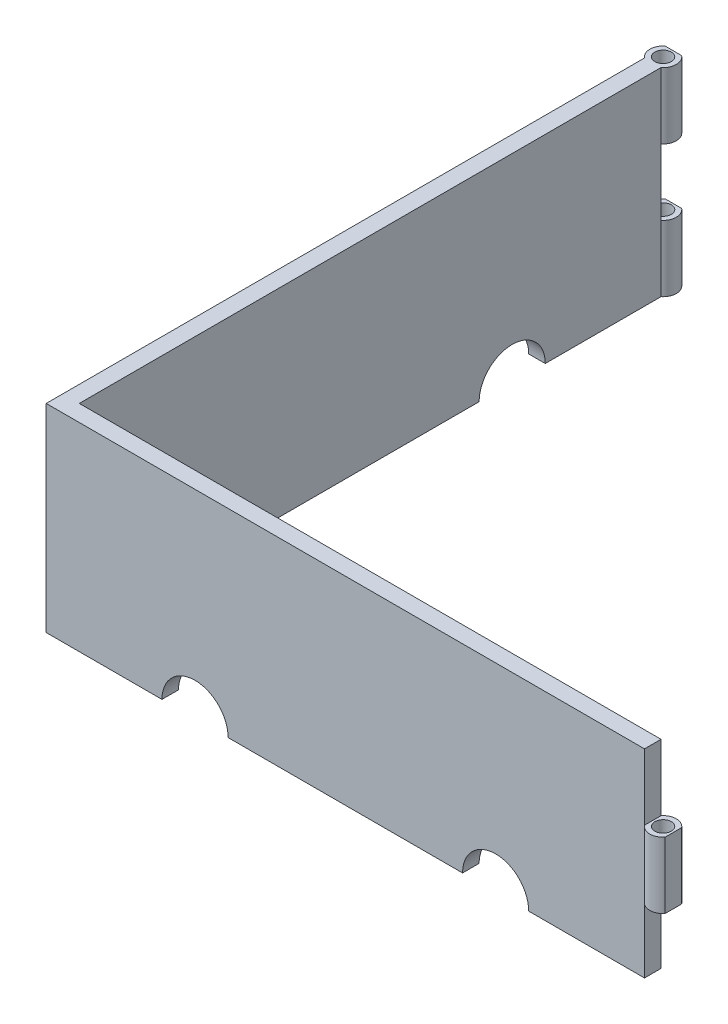
SolidWorks part; units mm, degrees
ref_plane "Front Plane" through (0, 0, 0) normal (0, 0, 1) x (1, 0, 0)
ref_plane "Top Plane" through (0, 0, 0) normal (0, 1, 0) x (1, 0, 0)
ref_plane "Right Plane" through (0, 0, 0) normal (1, 0, 0) x (0, 0, -1)
sketch "Sketch1" plane through (0, 0, 0) normal (0, 1, 0) x (1, 0, 0)
  line L0 (0, 0) -> (180, 0)
  line L1 (0, 0) -> (0, 180)
  line L3 (5, 180) -> (5, 5)
  line L4 (5, 5) -> (180, 5)
  line L6 (180, 5) -> (180.8775, 5)
  line L7 (180, 0) -> (180.8775, 0)
  line L8 (5, 180) -> (5, 180.8775)
  line L9 (0, 180) -> (0, 180.8775)
  arc A0 (180.8775, 0) -> (180.8775, 5) centre (184, 2.5) ccw
  arc A1 (5, 180.8775) -> (0, 180.8775) centre (2.5, 184) ccw
  dimension "D6" = 4
  dimension "D9" = 4
  dimension "D12" = 2.5
  dimension "D1" = 180
  dimension "D2" = 180
  dimension "D3" = 5
  dimension "D4" = 5
  dimension "D5" = 0.8775
  dimension "D7" = 0.8775
  dimension "D8" = 3.1225
  dimension "D10" = 0.8775
  dimension "D11" = 0.8775
extrude "Boss-Extrude1" add sketch "Sketch1" along normal blind 60
sketch "Sketch2" plane through (0, 60, 0) normal (0, 1, 0) x (1, 0, 0)
  circle A0 centre (184, 2.5) radius 2.5
  circle A1 centre (2.5, 184) radius 2.5
  dimension "D1" = 5
  dimension "D2" = 5
extrude "Cut-Extrude1" cut sketch "Sketch2" against normal blind 50
sketch "Sketch4" plane through (0, 0, 0) normal (0, 0, 1) x (1, 0, 0)
  line L0 (180.8775, 0) -> (188, 0)
  line L1 (188, 0) -> (188, 20)
  line L2 (188, 0) -> (188, 60) construction
  line L3 (188, 20) -> (180.8775, 20)
  line L4 (180.8775, 60) -> (180.8775, 0) construction
  line L5 (180.8775, 20) -> (180.8775, 0)
  line L6 (180.8775, 60) -> (188, 60)
  line L7 (188, 60) -> (188, 40)
  line L8 (188, 40) -> (180.8775, 40)
  line L9 (180.8775, 40) -> (180.8775, 60)
  line L10 (180.8775, 0) -> (135.8775, 0)
  line L11 (0, 0) -> (180.8775, 0) construction
  line L12 (0, 0) -> (45, 0)
  circle A0 centre (135.8775, 0) radius 10
  circle A1 centre (45, 0) radius 10
  line M7 (0, 0) -> (180.8775, 0)
  line M8 (180.8775, 0) -> (180.8775, 60)
  dimension "D4" = 20
  dimension "D6" = 20
  dimension "D1" = 20
  dimension "D2" = 20
  dimension "D3" = 45
  dimension "D5" = 45
extrude "Cut-Extrude3" cut sketch "Sketch4" against normal through all both and the other way through all contours A1 L12 M7 | A0 M7 | L1 L3 L0 M8 | L8 L7 L6 M8 region at (184.4388, 10, 0) region at (184.4388, 50, 0) region at (45, 4.2441, 0) region at (135.8775, 4.2441, 0)
sketch "Sketch5" plane through (0, 40, 0) normal (0, 1, 0) x (1, 0, 0)
  line L0 (181.5, 2.5) -> (180.8775, 2.5)
  line L1 (180.8775, 5) -> (180.8775, 0) construction
  line L2 (186.5, 2.5) -> (187.1225, 2.5)
  line L3 (187.1225, 2.5) -> (187.1225, 5)
  line L4 (187.1225, 5) -> (188.4607, 5)
  line L5 (188.4607, 5) -> (188.4607, -0.6564)
  line L6 (188.4607, -0.6564) -> (187.1225, -0.6564)
  line L7 (187.1225, -0.6564) -> (187.1225, 2.5)
  circle A0 centre (184, 2.5) radius 2.5 construction
  arc A1 (180.8775, 0) -> (180.8775, 5) centre (184, 2.5) ccw construction
  arc M9 (180.8775, 0) -> (180.8775, 5) centre (184, 2.5) ccw
  dimension "D1" = 5.6564
  dimension "D2" = 1.3382
extrude "Cut-Extrude4" cut sketch "Sketch5" against normal through all both contours L7 L3 M9 region at (187.477, 40, -2.5)
sketch "Sketch6" plane through (0, 0, 0) normal (-1, 0, 0) x (0, 0, 1)
  line L0 (0, 0) -> (-45, 0)
  line L1 (-180.8775, 0) -> (0, 0) construction
  line L2 (-180.8775, 0) -> (-135.8775, 0)
  line L3 (-180.8775, 0) -> (-180.8775, 20)
  line L4 (-180.8775, 60) -> (-180.8775, 0) construction
  line L5 (-180.8775, 20) -> (-180.8775, 40)
  line L6 (-180.8775, 40) -> (-189.3831, 40)
  line L7 (-189.3831, 40) -> (-189.3831, 20)
  line L8 (-189.3831, 20) -> (-180.8775, 20)
  circle A0 centre (-45, 0) radius 10
  circle A1 centre (-135.8775, 0) radius 10
  line M6 (-180.8775, 0) -> (0, 0)
  line M9 (-180.8775, 60) -> (-180.8775, 0)
  dimension "D2" = 20
  dimension "D4" = 20
  dimension "D1" = 45
  dimension "D3" = 45
  dimension "D5" = 20
  dimension "D6" = 20
  dimension "D7" = 8.5056
extrude "Cut-Extrude6" cut sketch "Sketch6" against normal through all both and the other way through all contours A1 L2 M6 | A0 M6 | L7 L8 L6 M9 region at (0, 4.2441, -45) region at (0, 30, -185.1303) region at (0, 4.2441, -135.8775)
sketch "Sketch7" plane through (0, 60, 0) normal (0, 1, 0) x (1, 0, 0)
  line L0 (0, 180.8775) -> (5, 180.8775)
  line L1 (5, 5) -> (5, 180.8775) construction
  line L2 (2.5, 180.8775) -> (2.5, 181.5)
  line L3 (2.5, 186.5) -> (2.5, 187.1225)
  line L4 (2.5, 187.1225) -> (5.6708, 187.1225)
  line L5 (5.6708, 187.1225) -> (5.6708, 188.6509)
  line L6 (5.6708, 188.6509) -> (0, 188.6509)
  line L7 (0, 188.6509) -> (-0.7692, 188.6509)
  line L8 (-0.7692, 188.6509) -> (-0.7692, 187.1225)
  line L9 (-0.7692, 187.1225) -> (2.5, 187.1225)
  arc A0 (5, 180.8775) -> (0, 180.8775) centre (2.5, 184) ccw construction
  circle A1 centre (2.5, 184) radius 2.5 construction
  circle A2 centre (2.5, 184) radius 2.5 construction
  arc M14 (5, 180.8775) -> (0, 180.8775) centre (2.5, 184) ccw
  dimension "D1" = 1.5284
  dimension "D2" = 5.6708
  dimension "D3" = 3.1708
  dimension "D4" = 0.7692
extrude "Cut-Extrude7" cut sketch "Sketch7" against normal through all both contours L9 L4 M14 region at (2.5, 60, -187.477)
